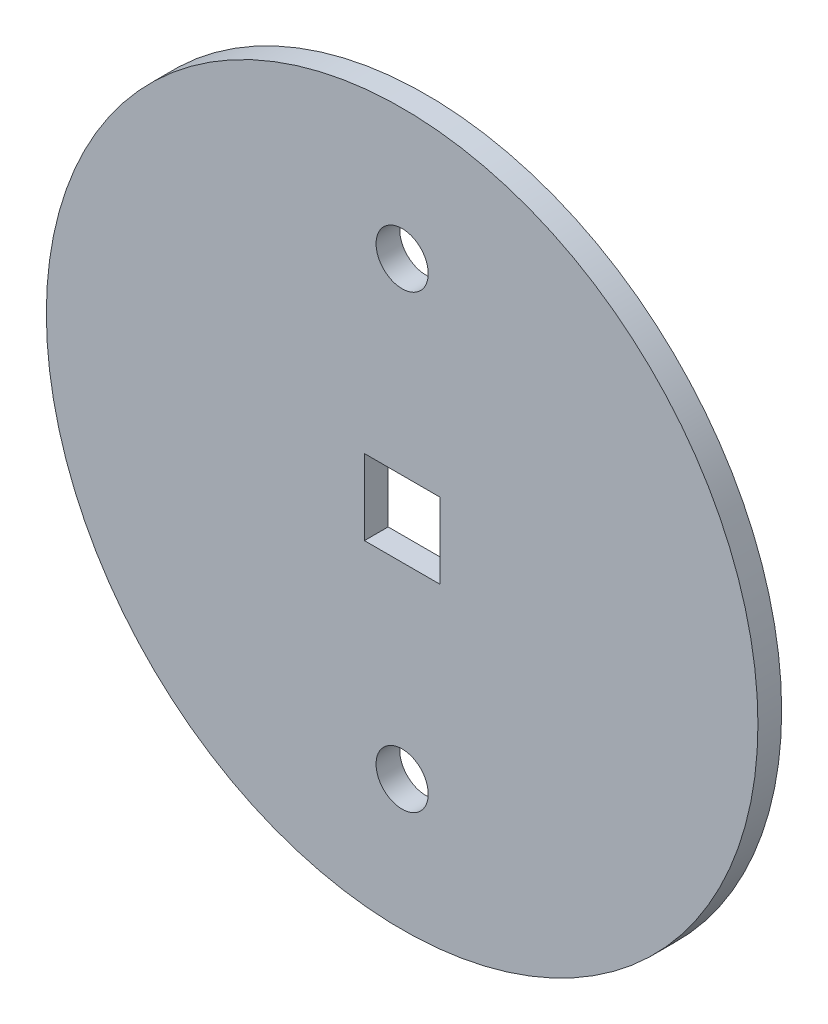
SolidWorks part; units mm, degrees
material "Plain Carbon Steel"
ref_plane "Front Plane" through (0, 0, 0) normal (0, 0, 1) x (1, 0, 0)
ref_plane "Top Plane" through (0, 0, 0) normal (0, 1, 0) x (1, 0, 0)
ref_plane "Right Plane" through (0, 0, 0) normal (1, 0, 0) x (0, 0, -1)
sketch "Sketch1" plane through (0, 0, 0) normal (0, 0, 1) x (1, 0, 0)
  line L2 (1.59, 0) -> (1.59, 1.59)
  line L3 (1.59, 0) -> (1.59, -1.59)
  line L4 (1.59, 1.59) -> (-1.59, 1.59)
  line L5 (-1.59, 1.59) -> (-1.59, -1.59)
  line L6 (-1.59, -1.59) -> (1.59, -1.59)
  circle A0 centre (0, 0) radius 15
  circle A1 centre (0, 9.5) radius 1.1
  circle A2 centre (0, -9.5) radius 1.1
  dimension "D1" = 30
  dimension "D3" = 9.5
  dimension "D7" = 2.2
  dimension "D8" = 2.2
  dimension "D2" = 1.59
  dimension "D4" = 1.59
  dimension "D5" = 1.59
  dimension "D6" = 9.5
base flange "Base-Flange1" sketch "Sketch1" thickness 1 reverse thickness direction no parameters "D1"=1.6
sketch "Bend-Lines1" [suppressed] plane through (0, 0, 0) normal (0, 1, 0) x (1, 0, 0)
sketch "Bounding-Box1" [suppressed] plane through (0, 0, 0) normal (0, 1, 0) x (1, 0, 0)
sheet metal parameters "Sheet-Metal8" thickness 1 parameters "D1"=1.6
flat pattern "Flat-Pattern8" [suppressed]
sketch "Bend-Lines2" plane through (0, 0, 0) normal (0, 1, 0) x (1, 0, 0)
sketch3d "Bounding-Box2" [suppressed]
  line L0 (-14.9498, 15.0499, 0) -> (-15.0498, -14.9499, 0) construction
  line L1 (15.0499, 14.9499, 0) -> (14.9499, -15.0499, 0) construction
  line L2 (-14.9498, 15.0499, 0) -> (15.0499, 14.9499, 0) construction
  line L3 (-15.0498, -14.9499, 0) -> (14.9499, -15.0499, 0) construction
